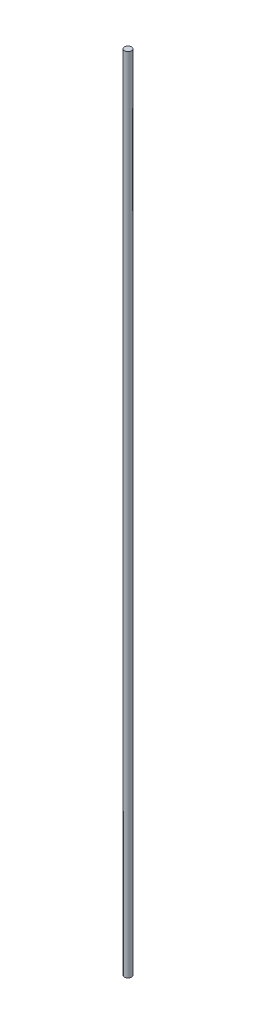
SolidWorks part; units mm, degrees
material "AISI 1020"
ref_plane "Front Plane" through (0, 0, 0) normal (0, 0, 1) x (1, 0, 0)
ref_plane "Top Plane" through (0, 0, 0) normal (0, 1, 0) x (1, 0, 0)
ref_plane "Right Plane" through (0, 0, 0) normal (1, 0, 0) x (0, 0, -1)
sketch "Sketch1" plane through (0, 0, 0) normal (0, 1, 0) x (1, 0, 0)
  circle A0 centre (0, 0) radius 3.175
  dimension "D1" = 6.35
extrude "Boss-Extrude1" [suppressed] add sketch "Sketch1" along normal blind 628.65
extrude "Boss-Extrude2" add sketch "Sketch1<2>" along normal blind 730.25
sketch "Sketch1<2>" plane through (0, 0, 0) normal (0, 1, 0) x (1, 0, 0) same geometry as "Sketch1"
equation "\"Diameter\"= 0.25"
equation "\"Length\"= 24.75"
equation "\"D1@Sketch1\"=\"Diameter\""
equation "\"D1@Boss-Extrude1\"=\"Length\""
